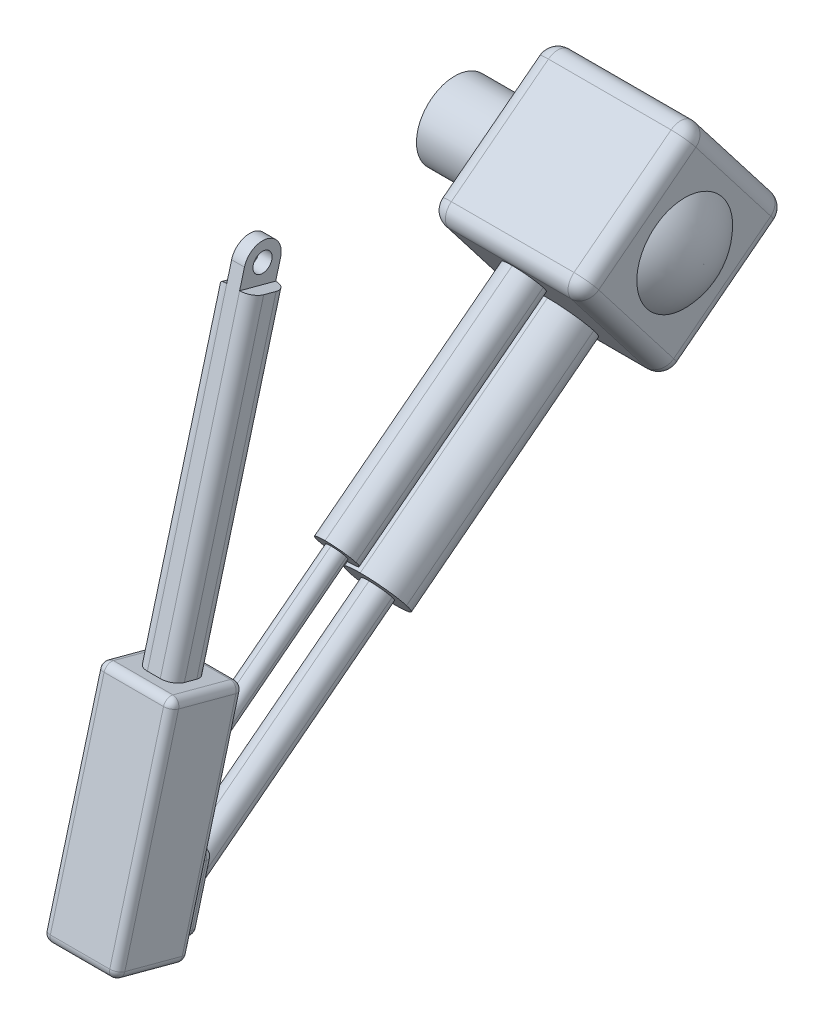
SolidWorks part; units mm, degrees
ref_plane "Front Plane" through (0, 0, 0) normal (0, 0, 1) x (1, 0, 0)
ref_plane "Top Plane" through (0, 0, 0) normal (0, 1, 0) x (1, 0, 0)
ref_plane "Right Plane" through (0, 0, 0) normal (1, 0, 0) x (0, 0, -1)
sketch "Sketch4" plane through (0, 0, 0) normal (1, 0, 0) x (0, 0, -1)
  line L0 (0, 0) -> (-615, -475) construction
  line L6 (-18.0162, -140.2691) -> (140.2691, -18.0162)
  line L7 (140.2691, -18.0162) -> (18.0162, 140.2691)
  line L8 (18.0162, 140.2691) -> (-140.2691, 18.0162)
  line L9 (-140.2691, 18.0162) -> (-18.0162, -140.2691)
  dimension "D5" = 475
  dimension "D6" = 615
  dimension "D7" = 100
  dimension "D8" = 200
  dimension "D9" = 100
  dimension "D10" = 200
extrude "Boss-Extrude1" add sketch "Sketch4" along normal blind 100
sketch3d "3DSketch1"
  point P0 (0, -22.2273, -44.9746)
ref_plane "Plane1" through (0, 0, 0) normal (-1, 0, 0) x (0, 0, 1)
sketch "Sketch5" plane through (0, 0, 0) normal (-1, 0, 0) x (0, 0, 1)
  circle A0 centre (0, 0) radius 50
  dimension "D1" = 100
extrude "Boss-Extrude2" add sketch "Sketch5" along normal blind 100
sketch3d "3DSketch2"
  point P0 (88.2846, -65.3334, 75.8934)
sketch3d "3DSketch3"
  point P0 (100, -36.6254, 42.4665)
ref_plane "Plane3" through (100, 0, 0) normal (1, 0, 0) x (0, 0, -1)
sketch "Sketch7" plane through (100, 0, 0) normal (1, 0, 0) x (0, 0, -1)
  line L0 (0, 0) -> (-79.1426, -61.1264) construction
  line L1 (-140.2691, 18.0162) -> (-18.0162, -140.2691) construction
  line L2 (-79.1426, -61.1264) -> (-323.3267, -249.7239) construction
  line L3 (-140.2691, 18.0162) -> (-18.0162, -140.2691)
  line L4 (-323.3267, -249.7239) -> (-79.1426, -61.1264)
  line L5 (-79.1426, -61.1264) -> (-33.2978, -120.4834)
  line L6 (-33.2978, -120.4834) -> (-277.4818, -309.0808)
  line L8 (-18.0162, -140.2691) -> (140.2691, -18.0162)
  line L9 (-338.6083, -229.9382) -> (-94.4243, -41.3408)
  line L10 (-94.4243, -41.3408) -> (-124.9875, -1.7694)
  line L11 (-124.9875, -1.7694) -> (-369.1715, -190.3669)
  line L13 (140.2691, -18.0162) -> (18.0162, 140.2691)
  line L14 (18.0162, 140.2691) -> (-140.2691, 18.0162)
  line L18 (-311.8655, -264.5631) -> (-549.3206, -447.9634)
  line L20 (-565.33, -507.7112) -> (-288.9431, -294.2416)
  line L21 (-288.9431, -294.2416) -> (-277.4818, -309.0808)
  line L22 (-277.4818, -309.0808) -> (-288.9431, -294.2416)
  line L23 (-346.2491, -220.0454) -> (-525.3066, -358.3418)
  line L25 (-514.6336, -318.5099) -> (-361.5307, -200.2597)
  line L26 (-361.5307, -200.2597) -> (-369.1715, -190.3669)
  line L27 (-311.8655, -264.5631) -> (-323.3267, -249.7239)
  line L28 (-338.6083, -229.9382) -> (-346.2491, -220.0454)
  line L29 (-33.2978, -120.4834) -> (-277.4818, -309.0808)
  line L30 (-33.2978, -120.4834) -> (-277.4818, -309.0808)
  line L31 (-288.9431, -294.2416) -> (-565.33, -507.7112)
  line L33 (-323.3267, -249.7239) -> (-79.1426, -61.1264)
  line L34 (-529.1888, -372.8307) -> (-510.7514, -304.0211)
  line L35 (-288.9431, -294.2416) -> (-311.8655, -264.5631)
  line L36 (-346.2491, -220.0454) -> (-361.5307, -200.2597)
  line L37 (-565.33, -507.7112) -> (-545.4383, -433.4745)
  line L38 (-545.4383, -433.4745) -> (-569.5865, -427.004)
  line L39 (-569.5865, -427.004) -> (-593.3604, -515.7296)
  line L40 (-593.3604, -515.7296) -> (-569.2122, -522.2)
  line L41 (-569.2122, -522.2) -> (-565.33, -507.7112)
  line L42 (-525.3066, -358.3418) -> (-529.1888, -372.8307)
  line L43 (-529.1888, -372.8307) -> (-553.337, -366.3602)
  line L44 (-553.337, -366.3602) -> (-534.8995, -297.5506)
  line L45 (-534.8995, -297.5506) -> (-510.7514, -304.0211)
  line L46 (-510.7514, -304.0211) -> (-514.6336, -318.5099)
  line L47 (0, 0) -> (4.8403, -507.7112) construction
  line L48 (-565.33, -507.7112) -> (4.8403, -507.7112) construction
  line L49 (-565.33, -507.7112) -> (-401.0607, 105.3499) construction
  dimension "D1" = 75
  dimension "D2" = 25
  dimension "D3" = 75
  dimension "D4" = 50
  dimension "D5" = 25
  dimension "D6" = 50
  dimension "D7" = 37.5
  dimension "D8" = 18.75
  dimension "D9" = 25
  dimension "D10" = 12.5
  dimension "D11" = 25
  dimension "D12" = 25
  dimension "D13" = 15
  dimension "D14" = 15
  dimension "D15" = 15
  dimension "D16" = 15
  dimension "D17" = 507.7112
  dimension "D18" = 570.1702
  dimension "D19" = 75
extrude "Boss-Extrude3" add sketch "Sketch7" along normal blind 100 contours L13 L14 L3 L8 region at (100, 0, 0)
extrude "Boss-Extrude4" add sketch "Sketch7<4>" along normal blind 37.5 contours L6 L3 L4 region at (100, -185.1036, 178.3122)
sketch "Sketch7<4>" plane through (100, 0, 0) normal (1, 0, 0) x (0, 0, -1) same geometry as "Sketch7"
extrude "Boss-Extrude5" add sketch "Sketch7<5>" against normal blind 37.5 contours L6 L3 L4 region at (100, -185.1036, 178.3122)
sketch "Sketch7<5>" plane through (100, 0, 0) normal (1, 0, 0) x (0, 0, -1) same geometry as "Sketch7"
extrude "Boss-Extrude6" add sketch "Sketch7<6>" along normal blind 25 contours L11 L9 L3 region at (100, -115.8538, 231.7979)
sketch "Sketch7<6>" plane through (100, 0, 0) normal (1, 0, 0) x (0, 0, -1) same geometry as "Sketch7"
extrude "Boss-Extrude7" add sketch "Sketch7<7>" against normal blind 25 contours L11 L9 L3 region at (100, -115.8538, 231.7979)
sketch "Sketch7<7>" plane through (100, 0, 0) normal (1, 0, 0) x (0, 0, -1) same geometry as "Sketch7"
extrude "Boss-Extrude8" add sketch "Sketch7<8>" along normal blind 18.75 contours L20 L35 L18 region at (100, -379.1844, 428.8211)
sketch "Sketch7<8>" plane through (100, 0, 0) normal (1, 0, 0) x (0, 0, -1) same geometry as "Sketch7"
extrude "Boss-Extrude9" add sketch "Sketch7<9>" against normal blind 18.75 contours L20 L35 L18 region at (100, -379.1844, 428.8211)
sketch "Sketch7<9>" plane through (100, 0, 0) normal (1, 0, 0) x (0, 0, -1) same geometry as "Sketch7"
extrude "Boss-Extrude10" add sketch "Sketch7<10>" along normal blind 12.5 contours L23 L36 L25 region at (100, -274.6774, 436.9)
sketch "Sketch7<10>" plane through (100, 0, 0) normal (1, 0, 0) x (0, 0, -1) same geometry as "Sketch7"
extrude "Boss-Extrude11" add sketch "Sketch7<11>" against normal blind 12.5 contours L23 L36 L25 region at (100, -274.6774, 436.9)
sketch "Sketch7<11>" plane through (100, 0, 0) normal (1, 0, 0) x (0, 0, -1) same geometry as "Sketch7"
extrude "Boss-Extrude12" add sketch "Sketch7<12>" along normal blind 27.5 contours L44 region at (100, -335.1906, 532.0442)
sketch "Sketch7<12>" plane through (100, 0, 0) normal (1, 0, 0) x (0, 0, -1) same geometry as "Sketch7"
extrude "Boss-Extrude13" add sketch "Sketch7<13>" against normal blind 27.5 contours L44 region at (100, -335.1906, 532.0442)
sketch "Sketch7<13>" plane through (100, 0, 0) normal (1, 0, 0) x (0, 0, -1) same geometry as "Sketch7"
extrude "Boss-Extrude14" add sketch "Sketch7<14>" along normal blind 33.75 contours L40 L39 L38 | L37 L38 L39 L40 L41 region at (100, -474.602, 569.3994)
sketch "Sketch7<14>" plane through (100, 0, 0) normal (1, 0, 0) x (0, 0, -1) same geometry as "Sketch7"
extrude "Boss-Extrude15" add sketch "Sketch7<15>" against normal blind 33.75 contours L40 L39 L38 | L37 L38 L39 L40 L41 region at (100, -474.602, 569.3994)
sketch "Sketch7<15>" plane through (100, 0, 0) normal (1, 0, 0) x (0, 0, -1) same geometry as "Sketch7"
sketch3d "3DSketch4"
  point P0 (112.8433, -498.5848, 588.7665)
sketch3d "3DSketch5"
  point P0 (115.3593, -447.5517, 575.0922)
ref_plane "Plane5" through (0, 113.7928, 424.6804) normal (0, 0.2588, 0.9659) x (1, 0, 0)
sketch "Sketch9" plane through (0, 113.7928, 424.6804) normal (0, 0.2588, 0.9659) x (1, 0, 0)
  line L0 (133.75, -559.8741) -> (133.75, -651.7295) construction
  line L1 (148.75, -666.7295) -> (51.25, -666.7295)
  line L2 (148.75, -666.7295) -> (148.75, -375.854)
  line L3 (148.75, -375.854) -> (51.25, -375.854)
  line L4 (51.25, -666.7295) -> (51.25, -375.854)
  line L5 (66.25, -559.8741) -> (66.25, -651.7295) construction
  line L6 (133.75, -651.7295) -> (66.25, -651.7295) construction
  line L7 (127.5, -425.854) -> (72.5, -425.854) construction
  dimension "D1" = 15
  dimension "D2" = 15
  dimension "D3" = 15
  dimension "D4" = 50
extrude "Boss-Extrude17" add sketch "Sketch9" along normal blind 48.75
sketch3d "3DSketch6"
  point P0 (118.8183, -516.3905, 648.8491)
sketch3d "3DSketch7"
  point P0 (81.2209, -327.1942, 593.3122)
ref_plane "Plane7" through (0, 126.4102, 471.7693) normal (0, 0.2588, 0.9659) x (1, 0, 0)
sketch "Sketch11" plane through (0, 126.4102, 471.7693) normal (0, 0.2588, 0.9659) x (1, 0, 0)
  line L1 (51.25, -666.7295) -> (148.75, -666.7295)
  line L2 (51.25, -666.7295) -> (51.25, -375.854)
  line L3 (51.25, -375.854) -> (148.75, -375.854)
  line L4 (148.75, -666.7295) -> (148.75, -375.854)
  line L5 (75.625, -375.854) -> (124.375, -375.854)
  line L6 (75.625, -375.854) -> (75.625, 24.146)
  line L7 (75.625, 24.146) -> (124.375, 24.146)
  line L8 (124.375, -375.854) -> (124.375, 24.146)
  dimension "D1" = 24.375
  dimension "D2" = 48.75
  dimension "D3" = 400
extrude "Boss-Extrude18" add sketch "Sketch11" along normal blind 48.75 contours L1 L4 L3 L2 region at (100, -377.1189, 606.6895)
extrude "Boss-Extrude19" add sketch "Sketch11<3>" along normal blind 24.375 contours L3 L8 L7 L6 region at (100, -43.4517, 517.2836)
sketch "Sketch11<3>" plane through (0, 126.4102, 471.7693) normal (0, 0.2588, 0.9659) x (1, 0, 0) same geometry as "Sketch11"
extrude "Boss-Extrude20" add sketch "Sketch11<4>" against normal blind 24.375 contours L3 L8 L7 L6 region at (100, -43.4517, 517.2836)
sketch "Sketch11<4>" plane through (0, 126.4102, 471.7693) normal (0, 0.2588, 0.9659) x (1, 0, 0) same geometry as "Sketch11"
sketch3d "3DSketch8"
  point P0 (200, -1.0695, -43.5413)
ref_plane "Plane8" through (200, 0, 0) normal (1, 0, 0) x (0, 0, -1)
sketch "Sketch12" plane through (200, 0, 0) normal (1, 0, 0) x (0, 0, -1)
  circle A0 centre (0, 0) radius 62.5
  dimension "D1" = 125
extrude "Boss-Extrude21" add sketch "Sketch12" along normal blind 25
fillet "Fillet1" radius 90 1 edges at (225, 62.5, 0)
sketch3d "3DSketch9"
  point P0 (124.375, 63.7852, 499.7315)
ref_plane "Plane9" through (124.375, 0, 0) normal (1, 0, 0) x (0, 0, -1)
sketch "Sketch13" plane through (124.375, 0, 0) normal (1, 0, 0) x (0, 0, -1)
  line L1 (-450.0386, 207.5101) -> (-493.4999, 45.3103) construction
  line L2 (-489.0643, 156.0422) -> (-441.9754, 143.4248) construction
  line L3 (-441.9754, 143.4248) -> (-435.6667, 166.9692)
  line L4 (-489.0643, 156.0422) -> (-482.7556, 179.5866)
  line L5 (-489.0643, 156.0422) -> (-441.9754, 143.4248)
  circle A0 centre (-459.2111, 173.2779) radius 24.375
  circle A1 centre (-459.2111, 173.2779) radius 12.5
  dimension "D1" = 48.75
  dimension "D3" = 25
  dimension "D2" = 24.375
extrude "Boss-Extrude22" add sketch "Sketch13" against normal blind 32.75 contours A0 L5 L3 | A0 L4 L5 | A0 region at (124.375, 150.093, 445.8253) region at (124.375, 152.7656, 447.3683) region at (124.375, 159.8921, 482.396)
extrude "Cut-Extrude1" cut sketch "Sketch13<4>" against normal blind 16 contours A0 L5 L3 | A0 A1 | A0 L4 L5 region at (124.375, 150.093, 445.8253) region at (124.375, 152.7656, 447.3683) region at (124.375, 159.8921, 482.396)
sketch "Sketch13<4>" plane through (124.375, 0, 0) normal (1, 0, 0) x (0, 0, -1) same geometry as "Sketch13"
fillet "Fillet2" radius 20 12 edges at (200, 61.1264, -79.1426) (0, 61.1264, -79.1426) (100, -140.2691, 18.0162) (200, -79.1426, -61.1264) (100, -18.0162, -140.2691) (0, -79.1426, -61.1264) (100, 140.2691, -18.0162) (200, 79.1426, 61.1264) (100, 18.0162, 140.2691) (0, 79.1426, 61.1264) (200, -61.1264, 79.1426) (0, -61.1264, 79.1426)
fillet "Fillet3" radius 25 4 edges at (125, -135.6395, 216.5163) (125, -96.0682, 247.0795) (75, -135.6395, 216.5163) (75, -96.0682, 247.0795)
fillet "Fillet4" radius 12.5 4 edges at (87.5, -289.1936, 435.7778) (112.5, -259.3848, 438.0822) (87.5, -259.3848, 438.0822) (112.5, -289.1936, 435.7778)
fillet "Fillet5" radius 37.5 4 edges at (62.5, -155.4251, 201.2347) (62.5, -214.7821, 155.3898) (137.5, -214.7821, 155.3898) (137.5, -155.4251, 201.2347)
fillet "Fillet6" radius 18.75 4 edges at (118.75, -400.9764, 427.1365) (81.25, -400.9764, 427.1365) (118.75, -356.2633, 430.593) (81.25, -356.2633, 430.593)
fillet "Fillet7" radius 10 28 edges at (148.75, -517.601, 644.3316) (148.75, -236.6369, 569.0474) (148.75, -389.7364, 559.6006) (51.25, -236.6369, 569.0474) (51.25, -517.601, 644.3316) (51.25, -389.7364, 559.6006) (51.25, -364.5015, 653.7784) (100, -224.0194, 616.1363) (148.75, -364.5015, 653.7784) (100, -504.9836, 691.4204) (100, -249.2543, 521.9586) (100, -530.2185, 597.2427) (133.75, -518.9648, 581.2863) (133.75, -430.2393, 557.5124) (66.25, -430.2393, 557.5124) (66.25, -518.9648, 581.2863) (72.5, -300.7858, 522.8254) (127.5, -369.5954, 541.2629) (127.5, -300.7858, 522.8254) (72.5, -369.5954, 541.2629) (127.5, -338.4259, 519.9701) (100, -372.8307, 529.1888) (72.5, -338.4259, 519.9701) (100, -304.0211, 510.7514) (133.75, -477.8373, 557.3253) (100, -433.4745, 545.4383) (66.25, -477.8373, 557.3253) (100, -522.2, 569.2122)
fillet "Fillet8" radius 16 5 edges at (75.625, 149.7335, 465.5198) (75.625, -49.7604, 493.7392) (75.625, -37.143, 540.8281) (124.375, -37.143, 540.8281) (124.375, -49.7604, 493.7392)
